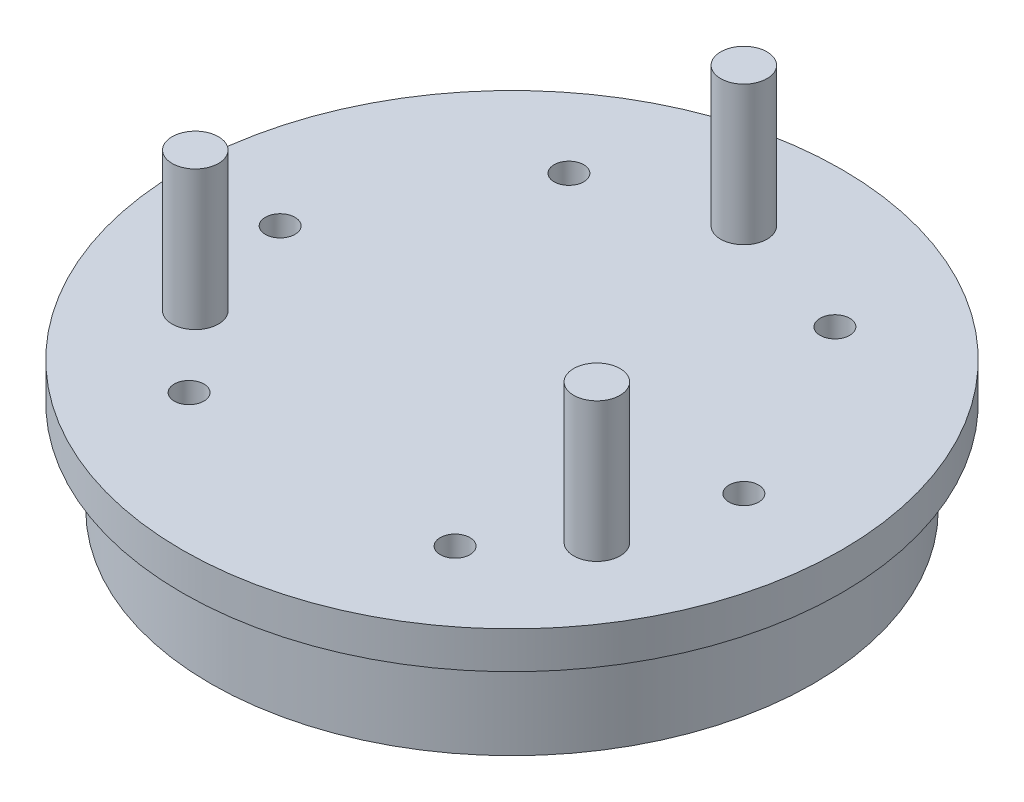
SolidWorks part; units mm, degrees
ref_plane "Front Plane" through (0, 0, 0) normal (0, 0, 1) x (1, 0, 0)
ref_plane "Top Plane" through (0, 0, 0) normal (0, 1, 0) x (1, 0, 0)
ref_plane "Right Plane" through (0, 0, 0) normal (1, 0, 0) x (0, 0, -1)
sketch "Sketch1" plane through (0, 0, 0) normal (0, 1, 0) x (1, 0, 0)
  line L0 (0, 0) -> (0, 25) construction
  line L1 (0, 0) -> (21.6506, -12.5) construction
  line L2 (0, 0) -> (-21.6506, -12.5) construction
  dimension "D1" = 25
  dimension "D2" = 120
  dimension "D3" = 120
sketch "Sketch3" plane through (0, 0, 0) normal (0, 1, 0) x (1, 0, 0)
  circle A0 centre (0, 0) radius 35.55
  dimension "D1" = 71.1
extrude "Boss-Extrude1" add sketch "Sketch3" along normal blind 4
sketch "Sketch4" plane through (0, 4, 0) normal (0, 1, 0) x (1, 0, 0)
  circle A0 centre (0, 25) radius 2.5
  circle A1 centre (21.6506, -12.5) radius 2.5
  circle A2 centre (-21.6506, -12.5) radius 2.5
  dimension "D1" = 5
extrude "Boss-Extrude2" add sketch "Sketch4" along normal blind 15
sketch "Sketch6" plane through (0, 0, 0) normal (0, -1, 0) x (1, 0, 0)
  circle A0 centre (0, 0) radius 32.5
  dimension "D1" = 65
extrude "Boss-Extrude4" add sketch "Sketch6" along normal blind 10
sketch "Sketch7" plane through (0, -10, 0) normal (0, -1, 0) x (1, 0, 0)
  line L0 (0, 0) -> (0, -25) construction
  line L1 (0, 0) -> (-14.3394, -20.4788) construction
  line L2 (0, 0) -> (14.3394, -20.4788) construction
  line L3 (0, 0) -> (0, 25) construction
  line L4 (0, 0) -> (-14.3394, 20.4788) construction
  line L5 (0, 0) -> (14.3394, 20.4788) construction
  line L6 (0, 0) -> (-25, 0) construction
  circle A1 centre (-25, 0) radius 1.6
  circle A2 centre (25, 0) radius 1.6
  circle A3 centre (-14.3394, -20.4788) radius 1.6
  circle A4 centre (14.3394, -20.4788) radius 1.6
  circle A5 centre (-14.3394, 20.4788) radius 1.6
  circle A6 centre (14.3394, 20.4788) radius 1.6
  dimension "D1" = 25
  dimension "D3" = 3.2
  dimension "D2" = 35
  dimension "D4" = 35
  dimension "D5" = 35
  dimension "D6" = 35
extrude "Cut-Extrude1" cut sketch "Sketch7" against normal through all
